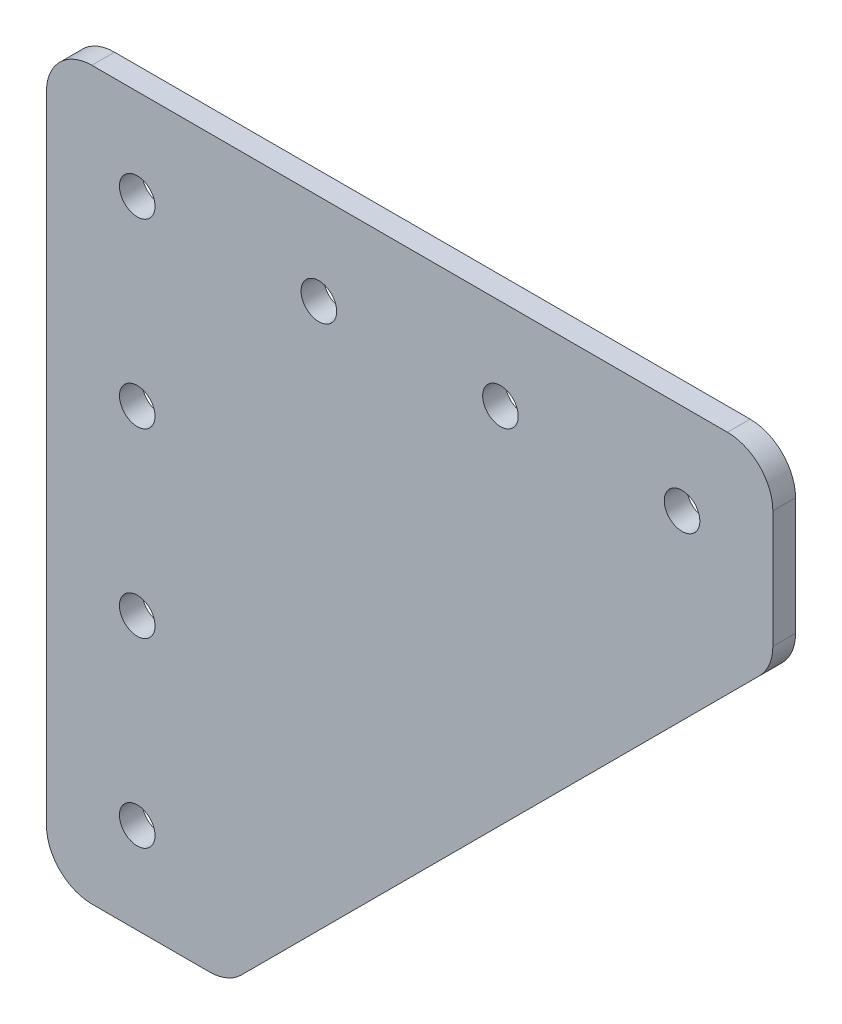
SolidWorks part; units mm, degrees
material "6061-T6 (SS)"
ref_plane "Front Plane" through (0, 0, 0) normal (0, 0, 1) x (1, 0, 0)
ref_plane "Top Plane" through (0, 0, 0) normal (0, 1, 0) x (1, 0, 0)
ref_plane "Right Plane" through (0, 0, 0) normal (1, 0, 0) x (0, 0, -1)
sketch "Sketch1" plane through (0, 0, 0) normal (0, 0, 1) x (1, 0, 0)
  line L0 (0, 0) -> (0, 101.6)
  line L1 (0, 101.6) -> (101.6, 101.6)
  line L2 (101.6, 101.6) -> (101.6, 76.2)
  line L5 (25.4, 0) -> (0, 0)
  line L6 (25.4, 0) -> (101.6, 76.2)
  dimension "D1" = 25.4
  dimension "D2" = 25.4
  dimension "D3" = 101.6
  dimension "D4" = 101.6
extrude "Boss-Extrude1" add sketch "Sketch1" along normal blind 3.175
sketch "Sketch2" plane through (0, 0, 3.175) normal (0, 0, 1) x (1, 0, 0)
  line L0 (101.6, 101.6) -> (0, 101.6) construction
  line L1 (0, 101.6) -> (0, 0) construction
  circle A0 centre (12.7, 88.9) radius 2.4892
  circle A5 centre (38.1, 88.9) radius 2.4892
  circle A6 centre (63.5, 88.9) radius 2.4892
  circle A8 centre (88.9, 88.9) radius 2.4892
  circle A9 centre (12.7, 63.5) radius 2.4892
  circle A10 centre (12.7, 38.1) radius 2.4892
  circle A11 centre (12.7, 12.7) radius 2.4892
  dimension "D1" = 12.7
  dimension "D2" = 25.4
  dimension "D3" = 25.4
  dimension "D4" = 25.4
  dimension "D5" = 12.7
  dimension "D6" = 4.9784
  dimension "D7" = 25.4
  dimension "D8" = 25.4
  dimension "D9" = 25.4
extrude "Cut-Extrude1" cut sketch "Sketch2" against normal through all
fillet "Fillet1" radius 6.35 5 edges at (25.4, 0, 1.5875) (0, 0, 1.5875) (0, 101.6, 1.5875) (101.6, 76.2, 1.5875) (101.6, 101.6, 1.5875)
